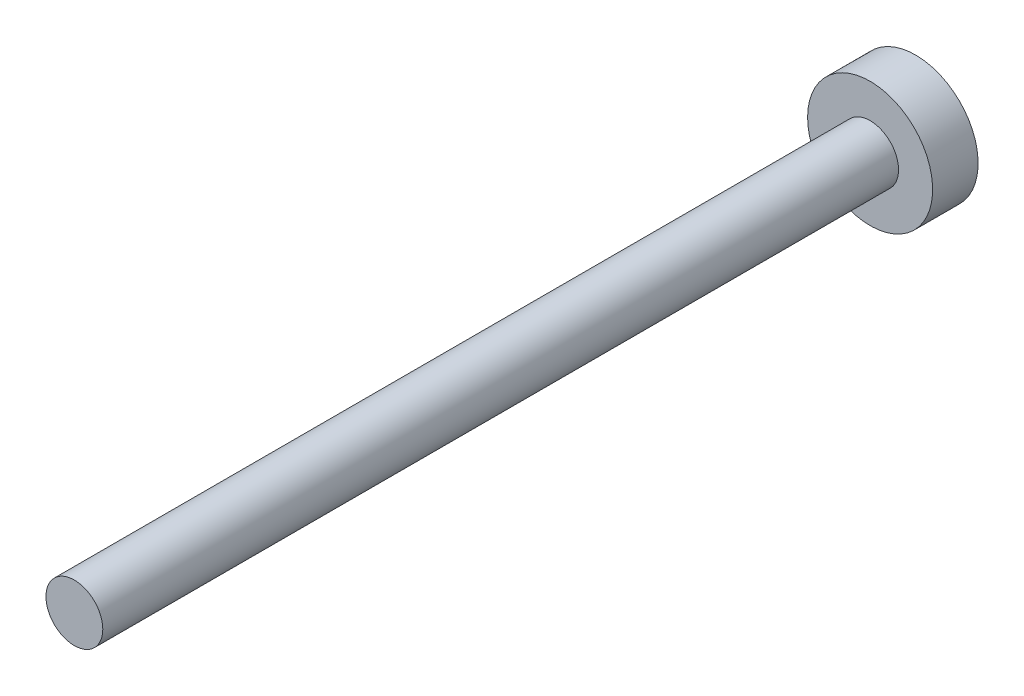
SolidWorks part; units mm, degrees
material "ABS"
ref_plane "Front Plane" through (0, 0, 0) normal (0, 0, 1) x (1, 0, 0)
ref_plane "Top Plane" through (0, 0, 0) normal (0, 1, 0) x (1, 0, 0)
ref_plane "Right Plane" through (0, 0, 0) normal (1, 0, 0) x (0, 0, -1)
sketch "Sketch1" plane through (0, 0, 0) normal (0, 0, 1) x (1, 0, 0)
  circle A0 centre (0, 0) radius 2.5
  dimension "D1" = 5
extrude "Boss-Extrude1" add sketch "Sketch1" along normal mid plane 70
sketch "Sketch2" plane through (0, 0, -35) normal (0, 0, -1) x (-1, 0, 0)
  circle A0 centre (0, 0) radius 5.5
  circle A1 centre (0, 0) radius 2.5 construction
  dimension "D1" = 3
extrude "Boss-Extrude2" add sketch "Sketch2" along normal blind 4
